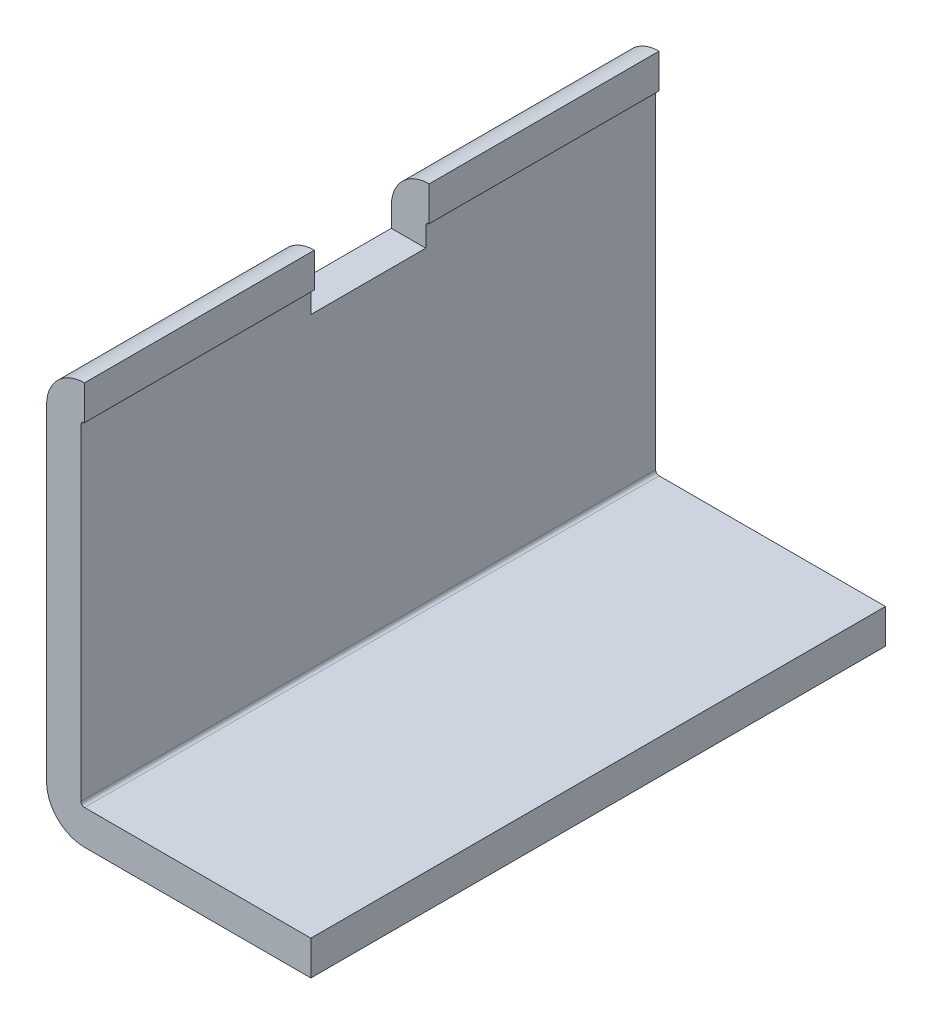
SolidWorks part; units mm, degrees
ref_plane "前视基准面" through (0, 0, 0) normal (0, 0, 1) x (1, 0, 0)
ref_plane "上视基准面" through (0, 0, 0) normal (0, 1, 0) x (1, 0, 0)
ref_plane "右视基准面" through (0, 0, 0) normal (1, 0, 0) x (0, 0, -1)
sketch "草图1" plane through (0, 0, 0) normal (0, 0, 1) x (1, 0, 0)
  line L1 (0, 0) -> (0, -2.84)
  line L2 (0.03, -2.87) -> (2, -2.87)
  arc A0 (0, 0) -> (0.03, 0.03) centre (0.03, 0) cw
  arc A1 (0, -2.84) -> (0.03, -2.87) centre (0.03, -2.84) ccw
  point P6 (0, -2.87)
  dimension "D3" = 0.03
  dimension "D4" = 0.03
  dimension "D2" = 2
  dimension "D1" = 2.9
extrude "拉伸-薄壁1" add sketch "草图1" along normal blind 5 thin thin type one direction wall 0.3
sketch "草图2" plane through (0.03, 0, 0) normal (1, 0, 0) x (0, 0, -1)
  line L0 (-2.5, 0.33) -> (-2.5, 0.03) construction
  line L1 (-5, 0.33) -> (0, 0.33) construction
  line L2 (-5, 0.03) -> (0, 0.03) construction
  line L4 (-2, -0.17) -> (-3, -0.17)
  line L5 (-2, -0.17) -> (-2, 0.33)
  line L6 (-2, 0.33) -> (-3, 0.33)
  line L7 (-3, -0.17) -> (-3, 0.33)
  line L8 (-2, -0.17) -> (-3, 0.33) construction
  line L9 (-2, 0.33) -> (-3, -0.17) construction
  point P6 (-2.5, 0.08)
  dimension "D1" = 1
  dimension "D2" = 0.5
extrude "切除-拉伸1" cut sketch "草图2" against normal through all both and the other way through all
equation "\"A\"= 12.6mm'宽度"
equation "\"B\"= 13.45mm'长度"
equation "\"C\"= 5.8mm'高度"
equation "\"D\"= 2.0mm'引脚宽度"
equation "\"E\"= 5.0mm'引脚长度"
equation "\"F\"= 0.3mm'引脚厚度"
equation "\"D2@草图1\"=\"D\""
equation "\"D3@草图1\"=0.1*\"F\""
equation "\"D4@草图1\"=0.1*\"F\""
equation "\"D5@拉伸-薄壁1\"=\"F\""
equation "\"D1@拉伸-薄壁1\"=\"E\""
equation "\"D1@草图2\"=0.2*\"E\""
equation "\"D2@草图2\"=0.1*\"E\""
equation "\"D1@圆角1\"=0.2*\"F\""
equation "\"D1@草图1\"=0.5*\"C\""
